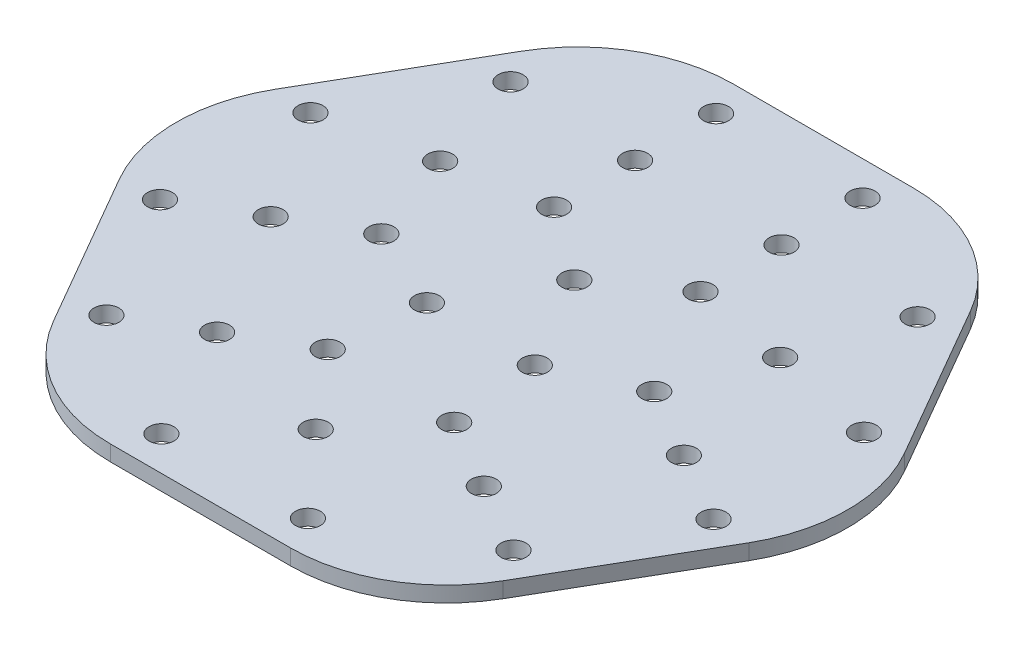
SolidWorks part; units mm, degrees
ref_plane "前视基准面" through (0, 0, 0) normal (0, 0, 1) x (1, 0, 0)
ref_plane "上视基准面" through (0, 0, 0) normal (0, 1, 0) x (1, 0, 0)
ref_plane "右视基准面" through (0, 0, 0) normal (1, 0, 0) x (0, 0, -1)
ref_axis "基准轴2" through (0, -75.8067, 0) along (0, 1, 0)
sketch "草图1" plane through (0, 0, 0) normal (0, 1, 0) x (1, 0, 0)
  line L1 (57.735, 100) -> (-57.735, 100)
  line L2 (-57.735, 100) -> (-115.4701, 0)
  line L3 (-115.4701, 0) -> (-57.735, -100)
  line L4 (-57.735, -100) -> (57.735, -100)
  line L5 (57.735, -100) -> (115.4701, 0)
  line L6 (115.4701, 0) -> (57.735, 100)
  circle A1 centre (0, 0) radius 100 construction
  dimension "D1" = 200
extrude "凸台-拉伸1" add sketch "草图1" along normal blind 5
sketch "草图2" plane through (0, 5, 0) normal (0, 1, 0) x (1, 0, 0)
  line L0 (23.5, 63) -> (23.5, 37) construction
  circle A1 centre (-23.5, 37) radius 4
  circle A3 centre (23.5, 37) radius 4
  circle A5 centre (-23.5, 63) radius 4
  circle A7 centre (23.5, 63) radius 4
  circle A16 centre (-23.5, 89) radius 4
  circle A17 centre (23.5, 89) radius 4
  circle A26 centre (23.5, 115) radius 4 [skipped]
  circle A27 centre (-23.5, 115) radius 4 [skipped]
  point P0 (23.5, 50)
  dimension "D2" = 26
  dimension "D3" = 8
  dimension "D4" = 8
  dimension "D5" = 47
  dimension "D6" = 26
  dimension "D7" = 23.5
  dimension "D8" = 47
  dimension "D9" = 50
  dimension "D10" = 2
  dimension "D11" = 0
  dimension "D12" = 8
  dimension "D13" = 8
  dimension "D14" = 26
extrude "切除-拉伸1" cut sketch "草图2" against normal through all contours A5 | A1 | A3 | A7 | A17 | A16 region at (-23.5, 5, -37) region at (23.5, 5, -37) region at (-23.5, 5, -63) region at (23.5, 5, -63)
pattern_circular "阵列(圆周)1" count 3 every 120 about axis through (0, -75.8067, 0) along (0, 1, 0) of "切除-拉伸1"
sketch "草图3" plane through (0, 5, 0) normal (0, 1, 0) x (1, 0, 0)
  line L0 (115.4701, 0) -> (57.735, 100) construction
  line L1 (86.6025, 50) -> (0, 0) construction
  circle A0 centre (65.3263, 64.8516) radius 4
  circle A1 centre (88.8263, 24.1484) radius 4
  circle A2 centre (54.5596, 31.5) radius 4
  dimension "D1" = 8
  dimension "D2" = 8
  dimension "D3" = 8
  dimension "D4" = 11
  dimension "D5" = 11
  dimension "D6" = 47
  dimension "D7" = 23.5
  dimension "D9" = 37
  dimension "D8" = 0
extrude "切除-拉伸2" cut sketch "草图3" against normal through all
pattern_circular "阵列(圆周)2" count 3 every 120 about axis through (0, -75.8067, 0) along (0, 1, 0) of "切除-拉伸2"
sketch "草图4" plane through (0, 5, 0) normal (0, 1, 0) x (1, 0, 0)
  circle A0 centre (0, 0) radius 20 construction
  circle A1 centre (0, 20) radius 4
  dimension "D1" = 40
  dimension "D2" = 8
extrude "切除-拉伸3" cut sketch "草图4" against normal through all
pattern_circular "阵列(圆周)3" count 3 over 360 about axis through (0, -75.8067, 0) along (0, 1, 0) of "切除-拉伸3"
fillet "圆角1" radius 50 6 edges at (57.735, 2.5, -100) (-57.735, 2.5, -100) (-115.4701, 2.5, 0) (-57.735, 2.5, 100) (57.735, 2.5, 100) (115.4701, 2.5, 0)
